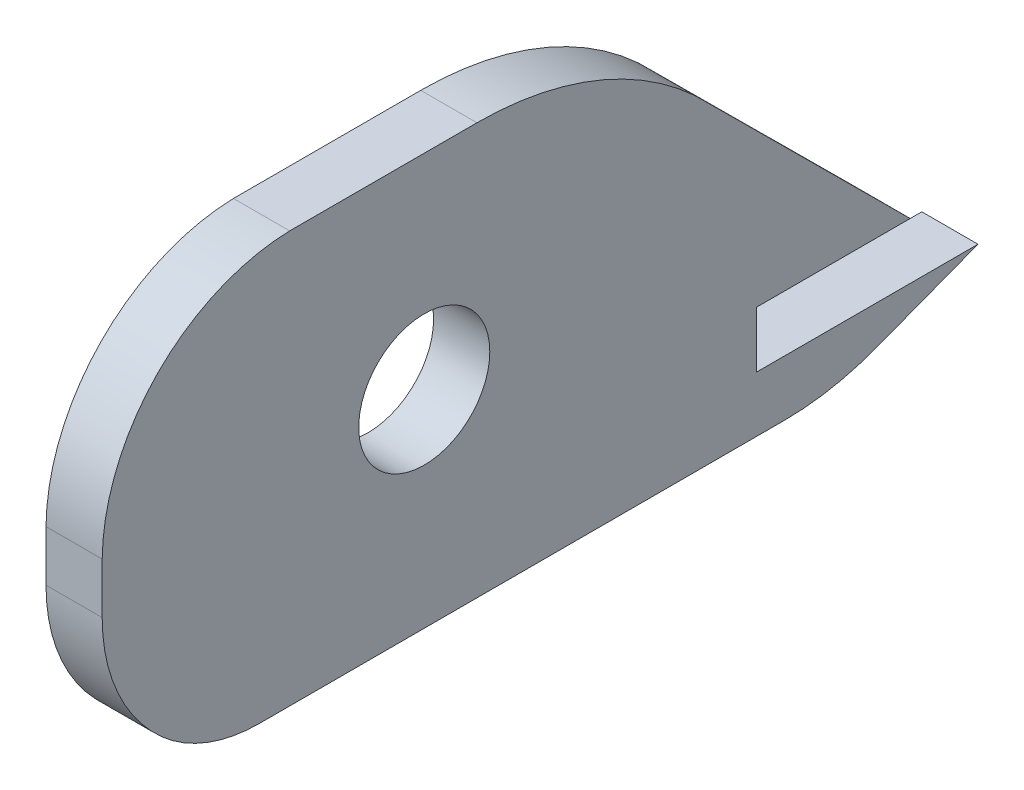
SolidWorks part; units mm, degrees
ref_plane "Front Plane" through (0, 0, 0) normal (0, 0, 1) x (1, 0, 0)
ref_plane "Top Plane" through (0, 0, 0) normal (0, 1, 0) x (1, 0, 0)
ref_plane "Right Plane" through (0, 0, 0) normal (1, 0, 0) x (0, 0, -1)
sketch "Sketch1" plane through (0, 0, 0) normal (0, 1, 0) x (1, 0, 0)
  line L8 (-9.9025, 36.4566) -> (-20.3157, 23.2959) construction
  line L10 (0, 0) -> (0, -15.9475) construction
  line L12 (-9.9025, 36.4566) -> (-20.3157, 23.2959)
  line L15 (-20.9631, 21.4344) -> (-20.9631, -5.9026) construction
  line L16 (-19.4729, -6.2109) -> (-9.8452, -11.8182)
  line L19 (-9.8452, -11.8182) -> (-9.8452, -21.8182)
  line L22 (-9.8452, -21.8182) -> (-6.8452, -21.8182)
  line L23 (-6.8452, -21.8182) -> (-6.8452, -12.4305)
  line L24 (-6.8452, -12.4305) -> (6.8452, -12.4305)
  line L25 (-4.1595, 37.5951) -> (-7.5499, 37.5951)
  line L26 (4.1595, 37.5951) -> (1.3957, 42.8144)
  line L27 (1.3957, 42.8144) -> (0, 43.4367)
  line L28 (24.762, -2.7815) -> (19.4729, -6.2109)
  line L29 (26.1299, 14.9044) -> (26.1299, -0.2643)
  line L30 (18.8536, 25.1438) -> (25.4825, 16.7659)
  line L31 (-18.8536, 25.1438) -> (-25.4825, 16.7659)
  line L32 (-26.1299, 14.9044) -> (-26.1299, -0.2643)
  line L33 (-24.762, -2.7815) -> (-19.4729, -6.2109)
  line L34 (4.1595, 37.5951) -> (7.5499, 37.5951)
  line L35 (6.8452, -21.8182) -> (6.8452, -12.4305)
  line L36 (9.8452, -21.8182) -> (6.8452, -21.8182)
  line L37 (9.8452, -11.8182) -> (9.8452, -21.8182)
  line L38 (19.4729, -6.2109) -> (9.8452, -11.8182)
  line L39 (0, 0) -> (0, 47.8638) construction
  line L40 (-1.3957, 42.8144) -> (0, 43.4367)
  line L41 (-4.1595, 37.5951) -> (-1.3957, 42.8144)
  line L42 (9.9025, 36.4566) -> (20.3157, 23.2959)
  arc A1 (-7.5499, 37.5951) -> (-9.9025, 36.4566) centre (-7.5499, 34.5951) ccw construction
  circle A4 centre (-5.0017, 34.5359) radius 1.5 construction
  circle A8 centre (-5.0017, 34.5359) radius 1.5
  arc A11 (-7.5499, 37.5951) -> (-9.9025, 36.4566) centre (-7.5499, 34.5951) ccw
  arc A12 (-19.7137, -6.0547) -> (-19.4729, -6.2109) centre (-17.9631, -3.6185) ccw
  arc A14 (25.4825, 16.7659) -> (26.1299, 14.9044) centre (23.1299, 14.9044) cw
  arc A15 (26.1299, -0.2643) -> (24.762, -2.7815) centre (23.1299, -0.2643) cw
  arc A16 (19.7137, -6.0547) -> (19.4729, -6.2109) centre (17.9631, -3.6185) cw
  arc A17 (-26.1299, -0.2643) -> (-24.762, -2.7815) centre (-23.1299, -0.2643) ccw
  arc A18 (-25.4825, 16.7659) -> (-26.1299, 14.9044) centre (-23.1299, 14.9044) ccw
  arc A19 (7.5499, 37.5951) -> (9.9025, 36.4566) centre (7.5499, 34.5951) cw
  circle A20 centre (5.0017, 34.5359) radius 1.5
  point P28 (0.1548, -12.4305)
  point P33 (-20.9631, -5.343)
  point P37 (0, -12.4305)
  point P41 (0.1548, -12.4305)
  point P46 (26.1299, 15.9477)
  point P48 (26.1299, -1.8946)
  point P49 (-0.1548, -12.4305)
  point P50 (20.9631, -5.343)
  point P54 (-26.1299, -1.8946)
  point P57 (-26.1299, 15.9477)
  dimension "D1" = 3
  dimension "D3" = 3
  dimension "D4" = 10
extrude "Boss-Extrude2" add sketch "Sketch1" along normal blind 3 contours A11 L12 A12 L16 L19 L22 L23 A8 region at (0, 0, -10.7329)
mirror "Mirror1" about plane through (0, 0, 0) normal (1, 0, 0) of "Boss-Extrude2"
sketch "Sketch3" plane through (9.8452, 0, 0) normal (1, 0, 0) x (0, 0, -1)
  line L0 (0, 0) -> (-5.4214, -2.0662)
  line L1 (-10.362, -2.9757) -> (-38.362, -2.9757)
  line L2 (-46.7647, 6.1171) -> (-46.7647, 8.8248)
  line L3 (-36.7549, 18.9944) -> (-26.7549, 18.9944)
  line L4 (-14.3131, 13.6377) -> (-3.6185, 3)
  line L5 (-3.6185, 3) -> (0, 0)
  line L6 (-11.8182, 3) -> (-11.8182, 0) construction
  arc A0 (-5.4214, -2.0662) -> (-10.362, -2.9757) centre (-10.362, 10.8976) cw
  arc A1 (-38.362, -2.9757) -> (-43.5481, -1.0139) centre (-38.362, 4.8597) cw
  arc A2 (-43.5481, -1.0139) -> (-46.7647, 6.1171) centre (-37.2518, 6.1171) cw
  circle A5 centre (-29.5682, 8.0684) radius 5 construction
  arc A7 (-26.7549, 18.9944) -> (-14.3131, 13.6377) centre (-26.7549, 1.8671) cw
  arc A8 (-36.7549, 18.9944) -> (-46.7647, 8.8248) centre (-36.4897, 8.7223) ccw
  dimension "D1" = 10
  dimension "D2" = 17.75
  dimension "D3" = 28
  dimension "D4" = 10
extrude "Boss-Extrude3" add sketch "Sketch3" against normal blind 3
sketch "Sketch4" plane through (9.8452, 0, 0) normal (1, 0, 0) x (0, 0, -1)
  circle A0 centre (-29.5682, 8.0684) radius 5
mirror "Mirror2" about plane through (0, 0, 0) normal (1, 0, 0) of "Boss-Extrude3"
extrude "Cut-Extrude1" cut sketch "Sketch4" against normal up to surface (3 mm away) rebuild error yes
sketch "Sketch5" plane through (-9.8452, 0, 0) normal (-1, 0, 0) x (0, 0, 1)
  line L0 (14.3482, 8.0684) -> (44.7882, 8.0684) construction
  line L1 (14.3482, 8.5684) -> (44.7882, 8.5684)
  line L2 (14.3482, 7.5684) -> (44.7882, 7.5684)
  line L3 (29.5682, 1.2134) -> (29.5682, 14.9234) construction
  line L4 (29.0682, 1.2134) -> (29.0682, 14.9234)
  line L5 (30.0682, 1.2134) -> (30.0682, 14.9234)
  circle A0 centre (29.5682, 8.0684) radius 5 construction
  circle A1 centre (29.5682, 8.0684) radius 5 construction
  arc A2 (14.3482, 8.5684) -> (14.3482, 7.5684) centre (14.3482, 8.0684) ccw
  arc A3 (44.7882, 7.5684) -> (44.7882, 8.5684) centre (44.7882, 8.0684) ccw
  arc A4 (29.0682, 1.2134) -> (30.0682, 1.2134) centre (29.5682, 1.2134) ccw
  arc A5 (30.0682, 14.9234) -> (29.0682, 14.9234) centre (29.5682, 14.9234) ccw
  circle A6 centre (29.5682, 8.0684) radius 3.5
  point P5 (29.5682, 8.0684)
  point P11 (29.5682, 8.0684)
  dimension "D1" = 0.5
  dimension "D2" = 0.5
  dimension "D5" = 10
  dimension "D6" = 7
  dimension "D3" = 30.44
  dimension "D4" = 13.71
extrude "Cut-Extrude2" cut sketch "Sketch5" against normal blind 3 contours L5 A6 L2 | L2 A6 L4 | L4 A6 L1 | L1 A6 L5 | L2 A3 L1 A2 | L5 A4 L4 A5 region at (-9.8452, 9.7725, 27.8641) region at (-9.8452, 6.3644, 27.8641) region at (-9.8452, 9.7725, 31.2723) region at (-9.8452, 6.3644, 31.2723)
sketch "Sketch7" plane through (0, 3, 0) normal (0, 1, 0) x (1, 0, 0)
  line L0 (-14.4326, 22.0478) -> (3.5367, 8.507)
  line L1 (3.5367, 8.507) -> (-3.6851, -1.0766)
  line L2 (-3.6851, -1.0766) -> (-21.6544, 12.4642)
  line L3 (-21.6544, 12.4642) -> (-14.4326, 22.0478)
  line L26 (-6.8452, -3.6185) -> (-6.8452, -12.4305)
  line L27 (-6.8452, -3.6185) -> (-6.8452, -12.4305)
  line L42 (6.8452, -3.6185) -> (9.8452, -3.6185)
  line L43 (6.8452, -3.6185) -> (9.8452, -3.6185)
  line L44 (-9.9025, 36.4566) -> (-25.4825, 16.7659)
  line L45 (-9.9025, 36.4566) -> (-25.4825, 16.7659)
  line L46 (-19.4729, -6.2109) -> (-9.8452, -11.8182)
  line L47 (-19.4729, -6.2109) -> (-9.8452, -11.8182)
  line L48 (-9.8452, -11.8182) -> (-9.8452, -3.6185)
  line L50 (-9.8452, -11.8182) -> (-9.8452, -3.6185)
  line L52 (-24.762, -2.7815) -> (-19.4729, -6.2109)
  line L53 (-24.762, -2.7815) -> (-19.4729, -6.2109)
  line L54 (-9.8452, -3.6185) -> (-6.8452, -3.6185)
  line L55 (-9.8452, -3.6185) -> (-6.8452, -3.6185)
  line L56 (-26.1299, 14.9044) -> (-26.1299, -0.2643)
  line L57 (-26.1299, 14.9044) -> (-26.1299, -0.2643)
  line L58 (0, 43.4367) -> (-1.3957, 42.8144)
  line L59 (0, 43.4367) -> (-1.3957, 42.8144)
  line L60 (-1.3957, 42.8144) -> (-4.1595, 37.5951)
  line L61 (-1.3957, 42.8144) -> (-4.1595, 37.5951)
  line L62 (-4.1595, 37.5951) -> (-7.5499, 37.5951)
  line L64 (-4.1595, 37.5951) -> (-7.5499, 37.5951)
  line L66 (-6.8452, -12.4305) -> (6.8452, -12.4305)
  line L68 (-6.8452, -12.4305) -> (6.8452, -12.4305)
  line L70 (6.8452, -12.4305) -> (6.8452, -3.6185)
  line L72 (6.8452, -12.4305) -> (6.8452, -3.6185)
  line L74 (9.8452, -3.6185) -> (9.8452, -11.8182)
  line L76 (9.8452, -3.6185) -> (9.8452, -11.8182)
  line L78 (9.8452, -11.8182) -> (19.4729, -6.2109)
  line L80 (9.8452, -11.8182) -> (19.4729, -6.2109)
  line L82 (19.4729, -6.2109) -> (24.762, -2.7815)
  line L83 (19.4729, -6.2109) -> (24.762, -2.7815)
  line L84 (26.1299, -0.2643) -> (26.1299, 14.9044)
  line L85 (26.1299, -0.2643) -> (26.1299, 14.9044)
  line L86 (25.4825, 16.7659) -> (9.9025, 36.4566)
  line L87 (25.4825, 16.7659) -> (9.9025, 36.4566)
  line L88 (7.5499, 37.5951) -> (4.1595, 37.5951)
  line L89 (7.5499, 37.5951) -> (4.1595, 37.5951)
  line L90 (4.1595, 37.5951) -> (1.3957, 42.8144)
  line L91 (4.1595, 37.5951) -> (1.3957, 42.8144)
  line L92 (1.3957, 42.8144) -> (0, 43.4367)
  line L93 (1.3957, 42.8144) -> (0, 43.4367)
  circle A0 centre (-20.1199, 18.8207) radius 1
  circle A1 centre (2.0023, 2.1505) radius 1
  arc A3 (-7.5499, 37.5951) -> (-9.9025, 36.4566) centre (-7.5499, 34.5951) ccw
  arc A18 (-7.5499, 37.5951) -> (-9.9025, 36.4566) centre (-7.5499, 34.5951) ccw
  arc A19 (-25.4825, 16.7659) -> (-26.1299, 14.9044) centre (-23.1299, 14.9044) ccw
  arc A20 (-25.4825, 16.7659) -> (-26.1299, 14.9044) centre (-23.1299, 14.9044) ccw
  arc A22 (-26.1299, -0.2643) -> (-24.762, -2.7815) centre (-23.1299, -0.2643) ccw
  arc A24 (-26.1299, -0.2643) -> (-24.762, -2.7815) centre (-23.1299, -0.2643) ccw
  arc A25 (24.762, -2.7815) -> (26.1299, -0.2643) centre (23.1299, -0.2643) ccw
  arc A26 (24.762, -2.7815) -> (26.1299, -0.2643) centre (23.1299, -0.2643) ccw
  arc A27 (26.1299, 14.9044) -> (25.4825, 16.7659) centre (23.1299, 14.9044) ccw
  arc A28 (26.1299, 14.9044) -> (25.4825, 16.7659) centre (23.1299, 14.9044) ccw
  arc A29 (9.9025, 36.4566) -> (7.5499, 37.5951) centre (7.5499, 34.5951) ccw
  arc A30 (9.9025, 36.4566) -> (7.5499, 37.5951) centre (7.5499, 34.5951) ccw
  dimension "D2" = 12
  dimension "D3" = 22.5
  dimension "D1" = 0
sketch "Sketch8" plane through (0, 3, 0) normal (0, 1, 0) x (1, 0, 0)
  line L0 (-14.4326, 22.0478) -> (3.5367, 8.507) construction
  line L1 (3.5367, 8.507) -> (-3.6851, -1.0766) construction
  line L2 (-3.6851, -1.0766) -> (-21.6544, 12.4642) construction
  line L3 (-21.6544, 12.4642) -> (-14.4326, 22.0478) construction
  line L4 (-14.4326, 22.0478) -> (3.5367, 8.507)
  line L5 (3.5367, 8.507) -> (-3.6851, -1.0766)
  line L6 (-3.6851, -1.0766) -> (-21.6544, 12.4642)
  line L7 (-21.6544, 12.4642) -> (-14.4326, 22.0478)
  line L28 (-24.762, -2.7815) -> (-19.4729, -6.2109)
  line L30 (-6.8452, -3.6185) -> (-6.8452, -12.4305)
  line L31 (-6.8452, -3.6185) -> (-6.8452, -12.4305)
  line L44 (-24.762, -2.7815) -> (-19.4729, -6.2109)
  line L48 (6.8452, -3.6185) -> (9.8452, -3.6185)
  line L49 (6.8452, -3.6185) -> (9.8452, -3.6185)
  line L50 (-9.9025, 36.4566) -> (-25.4825, 16.7659)
  line L51 (-9.9025, 36.4566) -> (-25.4825, 16.7659)
  line L52 (-26.1299, 14.9044) -> (-26.1299, -0.2643)
  line L53 (-26.1299, 14.9044) -> (-26.1299, -0.2643)
  line L54 (-19.4729, -6.2109) -> (-9.8452, -11.8182)
  line L55 (-19.4729, -6.2109) -> (-9.8452, -11.8182)
  line L56 (-9.8452, -11.8182) -> (-9.8452, -3.6185)
  line L57 (-9.8452, -11.8182) -> (-9.8452, -3.6185)
  line L58 (-9.8452, -3.6185) -> (-6.8452, -3.6185)
  line L59 (-9.8452, -3.6185) -> (-6.8452, -3.6185)
  line L60 (0, 43.4367) -> (-1.3957, 42.8144)
  line L61 (0, 43.4367) -> (-1.3957, 42.8144)
  line L62 (-1.3957, 42.8144) -> (-4.1595, 37.5951)
  line L63 (-1.3957, 42.8144) -> (-4.1595, 37.5951)
  line L64 (-4.1595, 37.5951) -> (-7.5499, 37.5951)
  line L66 (-4.1595, 37.5951) -> (-7.5499, 37.5951)
  line L68 (-6.8452, -12.4305) -> (6.8452, -12.4305)
  line L70 (-6.8452, -12.4305) -> (6.8452, -12.4305)
  line L72 (6.8452, -12.4305) -> (6.8452, -3.6185)
  line L74 (6.8452, -12.4305) -> (6.8452, -3.6185)
  line L76 (9.8452, -3.6185) -> (9.8452, -11.8182)
  line L78 (9.8452, -3.6185) -> (9.8452, -11.8182)
  line L80 (9.8452, -11.8182) -> (19.4729, -6.2109)
  line L82 (9.8452, -11.8182) -> (19.4729, -6.2109)
  line L84 (19.4729, -6.2109) -> (24.762, -2.7815)
  line L85 (19.4729, -6.2109) -> (24.762, -2.7815)
  line L86 (26.1299, -0.2643) -> (26.1299, 14.9044)
  line L87 (26.1299, -0.2643) -> (26.1299, 14.9044)
  line L88 (25.4825, 16.7659) -> (9.9025, 36.4566)
  line L89 (25.4825, 16.7659) -> (9.9025, 36.4566)
  line L90 (7.5499, 37.5951) -> (4.1595, 37.5951)
  line L91 (7.5499, 37.5951) -> (4.1595, 37.5951)
  line L92 (4.1595, 37.5951) -> (1.3957, 42.8144)
  line L93 (4.1595, 37.5951) -> (1.3957, 42.8144)
  line L94 (1.3957, 42.8144) -> (0, 43.4367)
  line L95 (1.3957, 42.8144) -> (0, 43.4367)
  circle A0 centre (-20.1199, 18.8207) radius 1 construction
  circle A1 centre (2.0023, 2.1505) radius 1 construction
  circle A2 centre (-20.1199, 18.8207) radius 1
  circle A3 centre (2.0023, 2.1505) radius 1
  arc A5 (-7.5499, 37.5951) -> (-9.9025, 36.4566) centre (-7.5499, 34.5951) ccw
  arc A18 (-7.5499, 37.5951) -> (-9.9025, 36.4566) centre (-7.5499, 34.5951) ccw
  arc A19 (-25.4825, 16.7659) -> (-26.1299, 14.9044) centre (-23.1299, 14.9044) ccw
  arc A20 (-25.4825, 16.7659) -> (-26.1299, 14.9044) centre (-23.1299, 14.9044) ccw
  arc A21 (-26.1299, -0.2643) -> (-24.762, -2.7815) centre (-23.1299, -0.2643) ccw
  arc A22 (-26.1299, -0.2643) -> (-24.762, -2.7815) centre (-23.1299, -0.2643) ccw
  arc A23 (24.762, -2.7815) -> (26.1299, -0.2643) centre (23.1299, -0.2643) ccw
  arc A24 (24.762, -2.7815) -> (26.1299, -0.2643) centre (23.1299, -0.2643) ccw
  arc A25 (26.1299, 14.9044) -> (25.4825, 16.7659) centre (23.1299, 14.9044) ccw
  arc A26 (26.1299, 14.9044) -> (25.4825, 16.7659) centre (23.1299, 14.9044) ccw
  arc A27 (9.9025, 36.4566) -> (7.5499, 37.5951) centre (7.5499, 34.5951) ccw
  arc A28 (9.9025, 36.4566) -> (7.5499, 37.5951) centre (7.5499, 34.5951) ccw
  dimension "D1" = 0
sketch "Sketch9" plane through (0, 3, 0) normal (0, 1, 0) x (1, 0, 0)
  line L0 (3.5367, 8.507) -> (-3.6851, -1.0766) construction
  line L1 (-14.4326, 22.0478) -> (3.5367, 8.507) construction
  line L2 (-3.6851, -1.0766) -> (-21.6544, 12.4642) construction
  line L3 (-21.6544, 12.4642) -> (-14.4326, 22.0478) construction
  line L4 (3.5367, 8.507) -> (-3.6851, -1.0766)
  line L5 (-14.4326, 22.0478) -> (3.5367, 8.507)
  line L6 (-3.6851, -1.0766) -> (-21.6544, 12.4642)
  line L7 (-21.6544, 12.4642) -> (-14.4326, 22.0478)
  line L28 (-24.762, -2.7815) -> (-19.4729, -6.2109)
  line L30 (-6.8452, -3.6185) -> (-6.8452, -12.4305)
  line L31 (-6.8452, -3.6185) -> (-6.8452, -12.4305)
  line L44 (-24.762, -2.7815) -> (-19.4729, -6.2109)
  line L48 (6.8452, -3.6185) -> (9.8452, -3.6185)
  line L49 (6.8452, -3.6185) -> (9.8452, -3.6185)
  line L50 (-9.9025, 36.4566) -> (-25.4825, 16.7659)
  line L51 (-26.1299, 14.9044) -> (-26.1299, -0.2643)
  line L52 (-19.4729, -6.2109) -> (-9.8452, -11.8182)
  line L53 (-19.4729, -6.2109) -> (-9.8452, -11.8182)
  line L54 (-9.8452, -11.8182) -> (-9.8452, -3.6185)
  line L55 (-9.8452, -11.8182) -> (-9.8452, -3.6185)
  line L56 (-9.8452, -3.6185) -> (-6.8452, -3.6185)
  line L57 (-9.8452, -3.6185) -> (-6.8452, -3.6185)
  line L58 (0, 43.4367) -> (-1.3957, 42.8144)
  line L59 (0, 43.4367) -> (-1.3957, 42.8144)
  line L60 (-1.3957, 42.8144) -> (-4.1595, 37.5951)
  line L61 (-1.3957, 42.8144) -> (-4.1595, 37.5951)
  line L62 (-4.1595, 37.5951) -> (-7.5499, 37.5951)
  line L63 (-4.1595, 37.5951) -> (-7.5499, 37.5951)
  line L64 (-6.8452, -12.4305) -> (6.8452, -12.4305)
  line L65 (-6.8452, -12.4305) -> (6.8452, -12.4305)
  line L66 (6.8452, -12.4305) -> (6.8452, -3.6185)
  line L67 (6.8452, -12.4305) -> (6.8452, -3.6185)
  line L68 (9.8452, -3.6185) -> (9.8452, -11.8182)
  line L69 (9.8452, -3.6185) -> (9.8452, -11.8182)
  line L70 (9.8452, -11.8182) -> (19.4729, -6.2109)
  line L71 (9.8452, -11.8182) -> (19.4729, -6.2109)
  line L72 (19.4729, -6.2109) -> (24.762, -2.7815)
  line L73 (19.4729, -6.2109) -> (24.762, -2.7815)
  line L74 (26.1299, -0.2643) -> (26.1299, 14.9044)
  line L75 (26.1299, -0.2643) -> (26.1299, 14.9044)
  line L76 (25.4825, 16.7659) -> (9.9025, 36.4566)
  line L77 (25.4825, 16.7659) -> (9.9025, 36.4566)
  line L78 (7.5499, 37.5951) -> (4.1595, 37.5951)
  line L79 (7.5499, 37.5951) -> (4.1595, 37.5951)
  line L80 (4.1595, 37.5951) -> (1.3957, 42.8144)
  line L81 (4.1595, 37.5951) -> (1.3957, 42.8144)
  line L82 (1.3957, 42.8144) -> (0, 43.4367)
  line L83 (1.3957, 42.8144) -> (0, 43.4367)
  circle A0 centre (2.0023, 2.1505) radius 1 construction
  circle A1 centre (-20.1199, 18.8207) radius 1 construction
  circle A2 centre (2.0023, 2.1505) radius 1
  circle A4 centre (-20.1199, 18.8207) radius 1
  arc A6 (-7.5499, 37.5951) -> (-9.9025, 36.4566) centre (-7.5499, 34.5951) ccw
  arc A21 (-7.5499, 37.5951) -> (-9.9025, 36.4566) centre (-7.5499, 34.5951) ccw
  arc A22 (-25.4825, 16.7659) -> (-26.1299, 14.9044) centre (-23.1299, 14.9044) ccw
  arc A23 (-26.1299, -0.2643) -> (-24.762, -2.7815) centre (-23.1299, -0.2643) ccw
  arc A24 (-26.1299, -0.2643) -> (-24.762, -2.7815) centre (-23.1299, -0.2643) ccw
  arc A25 (24.762, -2.7815) -> (26.1299, -0.2643) centre (23.1299, -0.2643) ccw
  arc A26 (24.762, -2.7815) -> (26.1299, -0.2643) centre (23.1299, -0.2643) ccw
  arc A27 (26.1299, 14.9044) -> (25.4825, 16.7659) centre (23.1299, 14.9044) ccw
  arc A28 (26.1299, 14.9044) -> (25.4825, 16.7659) centre (23.1299, 14.9044) ccw
  arc A29 (9.9025, 36.4566) -> (7.5499, 37.5951) centre (7.5499, 34.5951) ccw
  arc A30 (9.9025, 36.4566) -> (7.5499, 37.5951) centre (7.5499, 34.5951) ccw
  dimension "D1" = 0
sketch "Sketch10" plane through (0, 3, 0) normal (0, 1, 0) x (1, 0, 0)
  line L16 (-6.8452, -3.6185) -> (-6.8452, -12.4305)
  line L17 (-6.8452, -12.4305) -> (6.8452, -12.4305)
  line L18 (6.8452, -12.4305) -> (6.8452, -3.6185)
  line L19 (6.8452, -3.6185) -> (9.8452, -3.6185)
  line L20 (9.8452, -3.6185) -> (9.8452, -11.8182)
  line L21 (9.8452, -11.8182) -> (19.4729, -6.2109)
  line L22 (19.4729, -6.2109) -> (24.762, -2.7815)
  line L23 (26.1299, -0.2643) -> (26.1299, 14.9044)
  line L24 (25.4825, 16.7659) -> (9.9025, 36.4566)
  line L25 (7.5499, 37.5951) -> (-7.5499, 37.5951)
  line L26 (-9.9025, 36.4566) -> (-25.4825, 16.7659)
  line L27 (-26.1299, 14.9044) -> (-26.1299, -0.2643)
  line L28 (-24.762, -2.7815) -> (-19.4729, -6.2109)
  line L29 (-19.4729, -6.2109) -> (-9.8452, -11.8182)
  line L30 (-9.8452, -11.8182) -> (-9.8452, -3.6185)
  line L31 (-9.8452, -3.6185) -> (-6.8452, -3.6185)
  line L32 (-6.8452, -3.6185) -> (-6.8452, -12.4305)
  line L33 (-6.8452, -12.4305) -> (6.8452, -12.4305)
  line L34 (6.8452, -12.4305) -> (6.8452, -3.6185)
  line L35 (6.8452, -3.6185) -> (9.8452, -3.6185)
  line L36 (9.8452, -3.6185) -> (9.8452, -11.8182)
  line L37 (9.8452, -11.8182) -> (19.4729, -6.2109)
  line L38 (19.4729, -6.2109) -> (24.762, -2.7815)
  line L39 (26.1299, -0.2643) -> (26.1299, 14.9044)
  line L40 (25.4825, 16.7659) -> (9.9025, 36.4566)
  line L41 (7.5499, 37.5951) -> (-7.5499, 37.5951)
  line L42 (-9.9025, 36.4566) -> (-25.4825, 16.7659)
  line L43 (-26.1299, 14.9044) -> (-26.1299, -0.2643)
  line L44 (-24.762, -2.7815) -> (-19.4729, -6.2109)
  line L45 (-19.4729, -6.2109) -> (-9.8452, -11.8182)
  line L46 (-9.8452, -11.8182) -> (-9.8452, -3.6185)
  line L47 (-9.8452, -3.6185) -> (-6.8452, -3.6185)
  arc A6 (24.762, -2.7815) -> (26.1299, -0.2643) centre (23.1299, -0.2643) ccw
  arc A7 (26.1299, 14.9044) -> (25.4825, 16.7659) centre (23.1299, 14.9044) ccw
  arc A8 (9.9025, 36.4566) -> (7.5499, 37.5951) centre (7.5499, 34.5951) ccw
  arc A9 (-7.5499, 37.5951) -> (-9.9025, 36.4566) centre (-7.5499, 34.5951) ccw
  arc A10 (-25.4825, 16.7659) -> (-26.1299, 14.9044) centre (-23.1299, 14.9044) ccw
  arc A11 (-26.1299, -0.2643) -> (-24.762, -2.7815) centre (-23.1299, -0.2643) ccw
  arc A12 (24.762, -2.7815) -> (26.1299, -0.2643) centre (23.1299, -0.2643) ccw
  arc A13 (26.1299, 14.9044) -> (25.4825, 16.7659) centre (23.1299, 14.9044) ccw
  arc A14 (9.9025, 36.4566) -> (7.5499, 37.5951) centre (7.5499, 34.5951) ccw
  arc A15 (-7.5499, 37.5951) -> (-9.9025, 36.4566) centre (-7.5499, 34.5951) ccw
  arc A16 (-25.4825, 16.7659) -> (-26.1299, 14.9044) centre (-23.1299, 14.9044) ccw
  arc A17 (-26.1299, -0.2643) -> (-24.762, -2.7815) centre (-23.1299, -0.2643) ccw
  dimension "D1" = 0
extrude "Cut-Extrude3" cut sketch "Sketch9" against normal blind 10 contours L7 L6 L4 L5 | A4 | A2 region at (-9.0588, 3, -10.4856) region at (2.0023, 3, -2.1505) region at (-20.1199, 3, -18.8207)
sketch "Sketch16" plane through (0, 3, 0) normal (0, 1, 0) x (1, 0, 0)
  circle A0 centre (13.2517, 13.6459) radius 1.5
  circle A1 centre (5.0017, 34.5359) radius 1.5 construction
  dimension "D1" = 3
  dimension "D2" = 20.89
  dimension "D3" = 8.25
extrude "Cut-Extrude4" cut sketch "Sketch16" against normal blind 10
sketch "Sketch18" plane through (6.8452, 0, 0) normal (-1, 0, 0) x (0, 0, 1)
  circle A0 centre (29.5682, 8.0684) radius 3.5
  dimension "D1" = 7
sketch "Sketch19" plane through (0, 3, 0) normal (0, 1, 0) x (1, 0, 0)
  circle A0 centre (0, -2.643) radius 1.5
  dimension "D1" = 3
extrude "Cut-Extrude6" cut sketch "Sketch19" against normal blind 10
extrude "Boss-Extrude4" add sketch "Sketch18" against normal blind 20
sketch "Sketch20" plane through (26.8452, 0, 0) normal (1, 0, 0) x (0, 0, -1)
  circle A0 centre (-29.5682, 8.0684) radius 1.5
  dimension "D1" = 3
extrude "Cut-Extrude7" cut sketch "Sketch20" against normal blind 12
sketch "Sketch21" plane through (-9.8452, 0, 0) normal (-1, 0, 0) x (0, 0, 1)
  line L1 (11.8182, 3) -> (-46.6791, 3)
  line L2 (11.8182, 3) -> (11.8182, 0)
  line L3 (11.8182, 0) -> (-46.6791, 0)
  line L4 (-46.6791, 3) -> (-46.6791, 0)
extrude "Cut-Extrude8" cut sketch "Sketch21" against normal through all both and the other way through all
sketch "Sketch22" plane through (0, 3, 0) normal (0, 1, 0) x (1, 0, 0)
  line L0 (6.8452, -11.8182) -> (-6.8452, -11.8182) construction
  line L1 (-6.8452, -11.8182) -> (6.8452, -11.8182)
  line L2 (-6.8452, -11.8182) -> (-6.8452, -13.6506)
  line L3 (-6.8452, -13.6506) -> (6.8452, -13.6506)
  line L4 (6.8452, -11.8182) -> (6.8452, -13.6506)
  line L5 (-6.8452, -3.6185) -> (-6.8452, -14.3131) construction
extrude "Cut-Extrude9" cut sketch "Sketch22" against normal through all both
sketch "Sketch23" plane through (26.8452, 0, 0) normal (1, 0, 0) x (0, 0, -1)
  circle A0 centre (-29.5682, 8.0684) radius 3.5
  dimension "D1" = 7
extrude "Cut-Extrude10" cut sketch "Sketch23" against normal up to surface (20 mm away) up to face at (6.8452, 5.0611, 22.9774)
sketch "Sketch24" plane through (0, 18.9944, 0) normal (0, 1, 0) x (1, 0, 0)
  line L1 (-16.0205, 1.9459) -> (-2.7077, 1.9459)
  line L2 (-16.0205, 1.9459) -> (-16.0205, -49.7259)
  line L3 (-16.0205, -49.7259) -> (-2.7077, -49.7259)
  line L4 (-2.7077, 1.9459) -> (-2.7077, -49.7259)
extrude "Cut-Extrude11" cut sketch "Sketch24" against normal through all both
